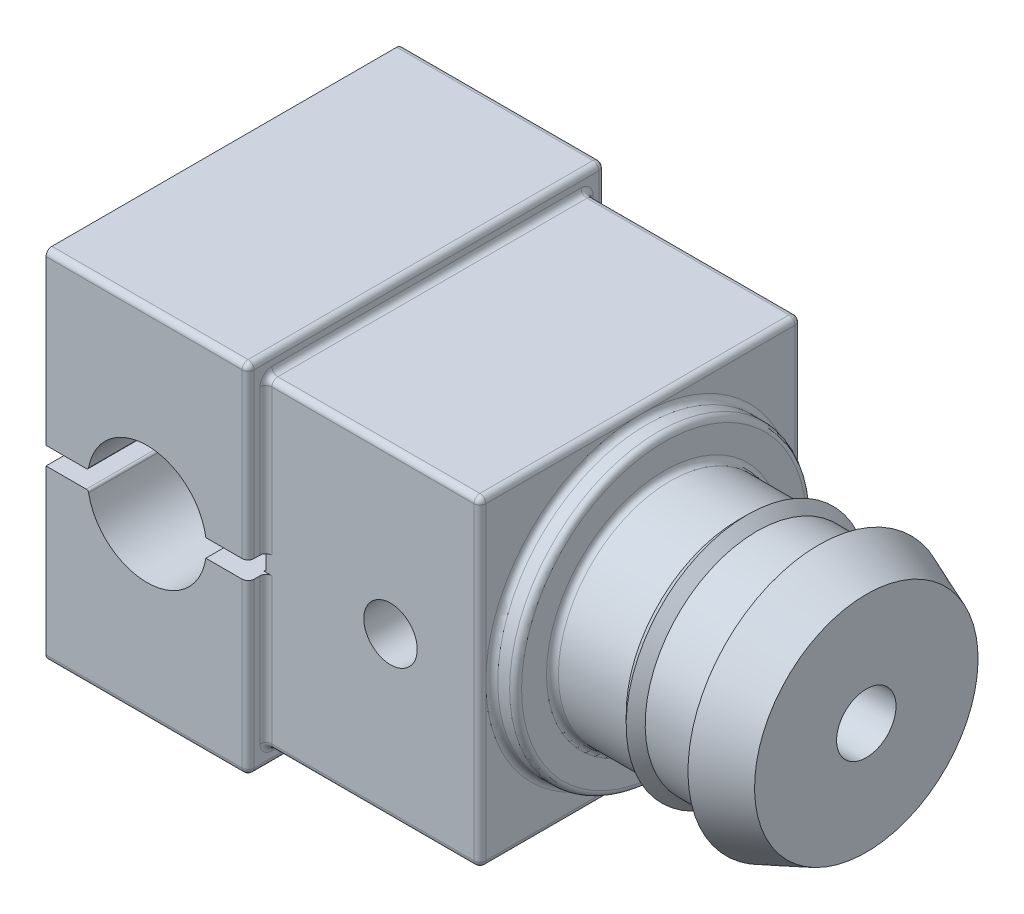
SolidWorks part; units mm, degrees
ref_plane "Front Plane" through (0, 0, 0) normal (0, 0, 1) x (1, 0, 0)
ref_plane "Top Plane" through (0, 0, 0) normal (0, 1, 0) x (1, 0, 0)
ref_plane "Right Plane" through (0, 0, 0) normal (1, 0, 0) x (0, 0, -1)
sketch "Sketch4" plane through (0, 0, 0) normal (0, 0, 1) x (1, 0, 0)
  line L0 (0, 0) -> (0, 9.4)
  line L1 (17, 9.4) -> (17, 0)
  line L2 (17, 0) -> (0, 0)
  line L3 (17, 9.4) -> (13, 11)
  line L4 (13, 11) -> (13, 9.4)
  line L5 (0, 9.4) -> (6.2, 9.4)
  line L6 (7.8, 9.4) -> (7, 10.2)
  line L7 (7, 10.2) -> (6.2, 9.4)
  line L8 (7.8, 9.4) -> (13, 9.4)
  line L9 (7, 10.2) -> (7, 9.4) construction
  line L10 (7.8, 9.4) -> (7, 9.4) construction
  point P9 (7, 9.4)
  dimension "D1" = 13
  dimension "D2" = 9.4
  dimension "D3" = 1.6
  dimension "D4" = 4
  dimension "D5" = 10
  dimension "D6" = 0.8
revolve "Revolve2" add sketch "Sketch4" angle 360 about L2
sketch "Sketch5" plane through (0, 0, 0) normal (-1, 0, 0) x (0, 0, 1)
  circle A0 centre (0, 0) radius 12.5
extrude "Boss-Extrude1" add sketch "Sketch5" along normal blind 2
sketch "Sketch6" plane through (-2, 0, 0) normal (-1, 0, 0) x (0, 0, 1)
  line L1 (-13.5, 13.5) -> (13.5, 13.5)
  line L2 (-13.5, 13.5) -> (-13.5, -13.5)
  line L3 (-13.5, -13.5) -> (13.5, -13.5)
  line L4 (13.5, 13.5) -> (13.5, -13.5)
  line L5 (-13.5, 13.5) -> (13.5, -13.5) construction
  line L6 (-13.5, -13.5) -> (13.5, 13.5) construction
  point P0 (0, 0)
  dimension "D1" = 27
  dimension "D2" = 27
extrude "Boss-Extrude2" add sketch "Sketch6" along normal blind 18
sketch "Sketch8" plane through (-20, 0, 0) normal (-1, 0, 0) x (0, 0, 1)
  line L1 (-15, -15) -> (15, -15)
  line L2 (-15, -15) -> (-15, 15)
  line L3 (-15, 15) -> (15, 15)
  line L4 (15, -15) -> (15, 15)
  line L5 (-15, -15) -> (15, 15) construction
  line L6 (-15, 15) -> (15, -15) construction
  point P0 (0, 0)
  dimension "D1" = 30
  dimension "D2" = 30
extrude "Boss-Extrude3" add sketch "Sketch8" along normal blind 17
sketch "Sketch9" plane through (0, 0, 13.5) normal (0, 0, 1) x (1, 0, 0)
  circle A0 centre (-9.5196, 0) radius 2.25
  dimension "D1" = 4.5
sketch "Sketch10" plane through (17, 0, 0) normal (1, 0, 0) x (0, 0, -1)
  circle A0 centre (0, 0) radius 2.5
extrude "Cut-Extrude2" cut sketch "Sketch10" against normal blind 26
sketch "Sketch11" plane through (0, 0, 15) normal (0, 0, 1) x (1, 0, 0)
  line L0 (-28.5, 15) -> (-28.5, -15) construction
  line L1 (-37, 15) -> (-20, 15) construction
  line L2 (-37, -15) -> (-20, -15) construction
  line L3 (-20, 0) -> (-37, 0) construction
  line L4 (-20, -15) -> (-20, 15) construction
  line L5 (-37, -15) -> (-37, 15) construction
  line L6 (-24.4692, 0.75) -> (-20, 0.75)
  line L7 (-20, 0.75) -> (-20, -0.75)
  line L8 (-20, -13.5) -> (-20, 13.5) construction
  line L9 (-20, -0.75) -> (-24.4692, -0.75)
  line L10 (-32.5308, 0.75) -> (-35.5028, 0.75)
  line L12 (-35.5028, -0.75) -> (-32.5308, -0.75)
  line L13 (-35.5028, 0.75) -> (-37, 0.75)
  line L14 (-37, 0.75) -> (-37, -0.75)
  line L15 (-37, -0.75) -> (-35.5028, -0.75)
  arc A0 (-24.4692, 0.75) -> (-32.5308, 0.75) centre (-28.5, 0) ccw
  arc A1 (-32.5308, -0.75) -> (-24.4692, -0.75) centre (-28.5, 0) ccw
  dimension "D1" = 0.75
  dimension "D5" = 4.1
  dimension "D2" = 0.75
  dimension "D3" = 0.75
  dimension "D4" = 0.75
extrude "Cut-Extrude3" cut sketch "Sketch11" against normal blind 24
sketch "Sketch12" plane through (-37, 0, 0) normal (-1, 0, 0) x (0, 0, 1)
  line L0 (0, -1.5122) -> (-8, -1.5122)
  line L1 (0, -16.5) -> (0, 16.5) construction
  dimension "D1" = 8
sketch "Sketch15" plane through (0, 0, 15) normal (0, 0, 1) x (1, 0, 0)
  circle A0 centre (-28.5, 0) radius 5
  dimension "D1" = 10
extrude "Cut-Extrude4" cut sketch "Sketch15" against normal blind 8 contours A0
fillet "Fillet3" radius 0.5 20 edges at (-20, 0, -13.5) (-20, 13.5, 0) (-11, 13.5, 13.5) (-20, 7.125, 13.5) (-20, 7.875, 15) (-20, -7.875, 15) (-20, -7.125, 13.5) (-20, -15, 0) (-20, -13.5, 0) (-11, -13.5, 13.5) (-11, -13.5, -13.5) (-11, 13.5, -13.5) (-2, 13.5, 0) (-2, 0, 13.5) (-2, -13.5, 0) (-2, 0, -13.5) (-2, 0, 12.5) (-20, 0, -15) (0, 0, 12.5) (0, 9.4, 0)
fillet "Fillet4" radius 0.5 9 edges at (-20.1464, -14.8536, -14.8536) (-20.1464, -14.8536, 14.8536) (-20.1464, 15, -14.8536) (-20, 15, 0) (-20.1464, 15, 14.8536) (-28.75, 15, -15) (-28.75, -15, -15) (-28.75, -15, 15) (-28.75, 15, 15)
fillet "Fillet6" radius 0.2 13 edges at (-32.9871, -0.75, 7) (-32.9871, 0.75, 7) (-28.5, 4.1, -9) (-34.7654, -0.75, -9) (-34.7654, 0.75, -9) (-33.4434, -0.75, 11) (-33.4434, 0.75, 11) (-28.5, -4.1, 7) (-28.5, -5, 7) (-28.5, 4.1, 7) (-28.5, 5, 7) (-20, -0.75, 2.25) (-20, 0.75, 2.25)
hole_wizard "#12-24 Tapped Hole1" positions "Sketch16" profile "Sketch17" tap size "#12-24" standard "ANSI Inch"
sketch "Sketch16" plane through (0, 0, 13.5) normal (0, 0, 1) x (1, 0, 0)
  point P0 (-9.5196, 0)
sketch "Sketch17" plane through (-9.5196, 0, 13.5) normal (1, 0, 0) x (0, -1, 0)
  line L0 (0, 0) -> (0, 16.8507)
  line L1 (0, 16.8507) -> (2.2479, 15.5)
  line L2 (2.2479, 15.5) -> (2.2479, 0)
  line L5 (2.2479, 0) -> (0, 0)
  line L10 (0, 16.8507) -> (-2.2479, 15.5) construction
  line L11 (0, -6.35) -> (0, 107.95) construction
  dimension "Tap Drill Dia." = 4.4958
  dimension "Tap Drill Depth" = 15.5
  dimension "Drill Angle" = 118
cosmetic thread "Hole Thread1" parameters "D1"=6.35, "D2"=5.4864
